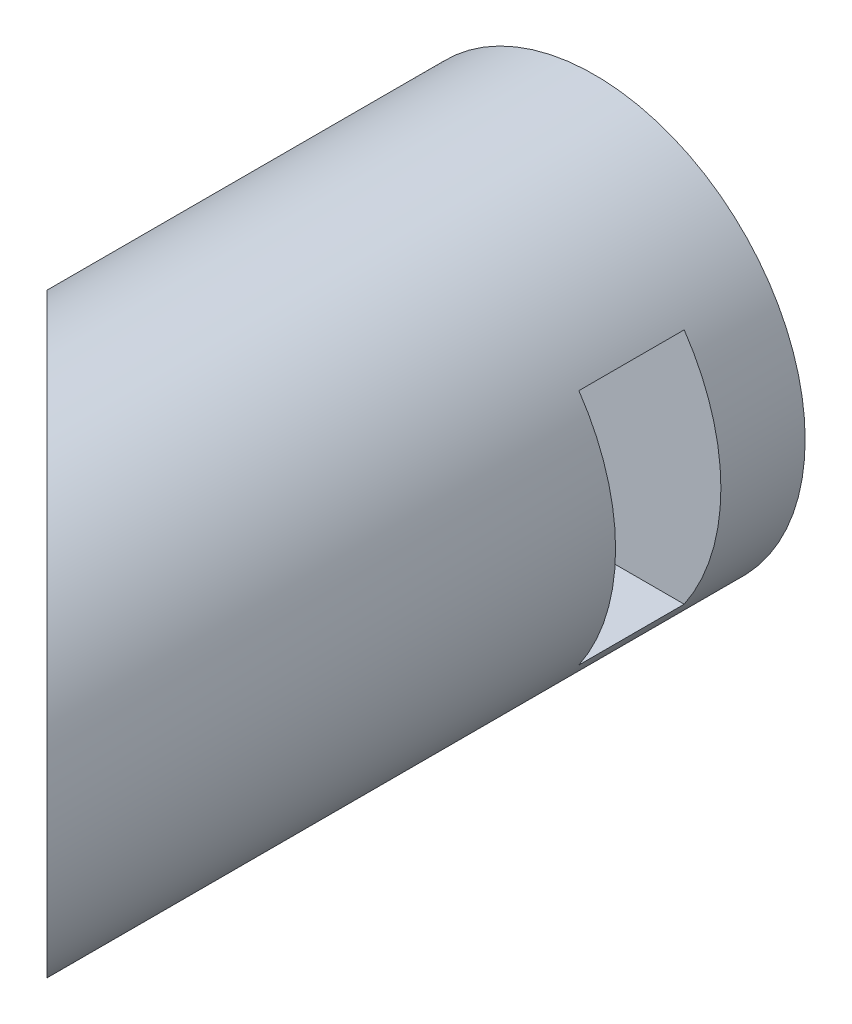
SolidWorks part; units mm, degrees
ref_plane "Płaszczyzna przednia" through (0, 0, 0) normal (0, 0, 1) x (1, 0, 0)
ref_plane "Płaszczyzna górna" through (0, 0, 0) normal (0, 1, 0) x (1, 0, 0)
ref_plane "Płaszczyzna prawa" through (0, 0, 0) normal (1, 0, 0) x (0, 0, -1)
sketch "Szkic1" plane through (0, 0, 0) normal (0, 0, 1) x (1, 0, 0)
  circle A0 centre (0, 0) radius 5
extrude "Dodanie-wyciągnięcie1" add sketch "Szkic1" along normal blind 18
sketch "Szkic2" plane through (0, 0, 0) normal (0, 1, 0) x (1, 0, 0)
  line L0 (-5, -18) -> (5, -18)
  line L1 (-5, -18) -> (5, -18) construction
  line L2 (5, -18) -> (-5, -8)
  line L3 (-5, 0) -> (-5, -18) construction
  line L4 (-5, -8) -> (-5, -18)
  point P5 (0, 0)
  point P9 (0, 0)
extrude "Wytnij-wyciągnięcie1" cut sketch "Szkic2" against normal blind 5 and the other way blind 5
sketch "Szkic3" plane through (0, 0, 0) normal (1, 0, 0) x (0, 0, -1)
  line L1 (-2, 2.82) -> (-4.5, 2.82)
  line L2 (-2, 2.82) -> (-2, -2.82)
  line L3 (-2, -2.82) -> (-4.5, -2.82)
  line L4 (-4.5, 2.82) -> (-4.5, -2.82)
  point P4 (0, 0)
  point P5 (0, 0)
  point P6 (0, 0)
extrude "Wytnij-wyciągnięcie2" cut sketch "Szkic3" against normal blind 3 and the other way blind 5
sketch "Szkic4" plane through (0, 0, 0) normal (0, 0, -1) x (-1, 0, 0)
  circle A0 centre (0, 0) radius 1.6
extrude "Wytnij-wyciągnięcie3" cut sketch "Szkic4" against normal up to next
sketch "Szkic5" plane through (0, 0, 2) normal (0, 0, 1) x (1, 0, 0)
  line L0 (-3, -2.82) -> (-3, 2.82)
  line L1 (-3, 2.82) -> (-4.3331, 0)
  line L2 (-4.3331, 0) -> (-3, -2.82)
extrude "Wytnij-wyciągnięcie4" cut sketch "Szkic5" along normal blind 2.5
